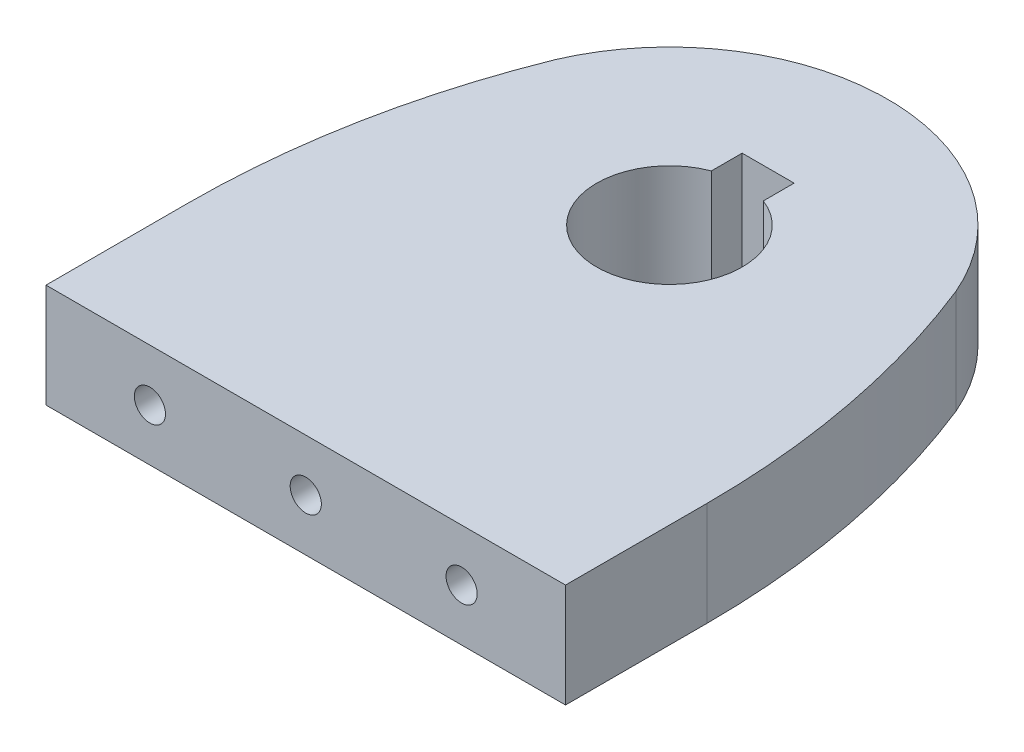
SolidWorks part; units mm, degrees
ref_plane "Alzado" through (0, 0, 0) normal (0, 0, 1) x (1, 0, 0)
ref_plane "Planta" through (0, 0, 0) normal (0, 1, 0) x (1, 0, 0)
ref_plane "Vista lateral" through (0, 0, 0) normal (1, 0, 0) x (0, 0, -1)
sketch "Croquis1" plane through (0, 0, 0) normal (0, 1, 0) x (1, 0, 0)
  line L5 (-25, 15) -> (-19.2969, 28.2844)
  line L6 (-25, 15) -> (25, 15)
  line L7 (-25, 15) -> (-25, -15)
  line L8 (-25, -15) -> (25, -15)
  line L9 (25, 15) -> (25, -15)
  line L10 (-25, 15) -> (25, -15) construction
  line L11 (-25, -15) -> (25, 15) construction
  line L12 (25, 15) -> (19.2969, 28.2844)
  circle A0 centre (0, 20) radius 21
  point P0 (0, 0)
  dimension "D3" = 42
  dimension "D1" = 50
  dimension "D2" = 30
  dimension "D4" = 20
extrude "Saliente-Extruir1" add sketch "Croquis1" along normal blind 10 contours A0 L6 L7 L8 L9 | L6 A0 | A0 L6 L12 | L6 A0 | A0 L5 L6 region at (-22.1608, 0, -18.383) region at (0, 0, 3.9772) region at (0, 0, -26.28) region at (0, 0, -8.3304) region at (22.1608, 0, -18.383)
sketch "Croquis2" plane through (0, 10, 0) normal (0, 1, 0) x (1, 0, 0)
  circle A0 centre (0, 20) radius 16
  dimension "D1" = 32
extrude "Cortar-Extruir1" cut sketch "Croquis2" against normal through all
fillet "Redondeo1" radius 80 2 edges at (25, 5, -15) (-25, 5, -15)
sketch "Croquis3" plane through (0, 0, 15) normal (0, 0, 1) x (1, 0, 0)
  line L0 (-25, 5) -> (25, 5) construction
  line L1 (-25, 10) -> (-25, 0) construction
  line L2 (25, 10) -> (25, 0) construction
  circle A0 centre (0, 5) radius 1.5
  dimension "D1" = 3
extrude "Cortar-Extruir2" cut sketch "Croquis3" against normal blind 15
pattern_linear "MatrizL1" count 2 spacing 15 along (1, 0, 0) count 2 spacing 15 along (-1, 0, 0) of "Cortar-Extruir2"
sketch "Sketch1" plane through (0, 10, 0) normal (0, 1, 0) x (1, 0, 0)
  line L1 (-2.5, 29.5) -> (2.5, 29.5)
  line L2 (-2.5, 29.5) -> (-2.5, 24.5)
  line L3 (-2.5, 24.5) -> (2.5, 24.5)
  line L4 (2.5, 29.5) -> (2.5, 24.5)
  line L5 (-2.5, 29.5) -> (2.5, 24.5) construction
  line L6 (-2.5, 24.5) -> (2.5, 29.5) construction
  circle A0 centre (0, 20) radius 7
  circle A1 centre (0, 20) radius 16 construction
  circle A2 centre (0, 20) radius 16
  point P3 (0, 27)
  circle M4 centre (0, 20) radius 16
  dimension "D1" = 14
  dimension "D2" = 5
extrude "Boss-Extrude1" add sketch "Sketch1" against normal up to surface (10 mm away) contours A0 L2 L1 L4 M4 region at (-15.5475, 10, -20) up to face at (0, 0, -4)
